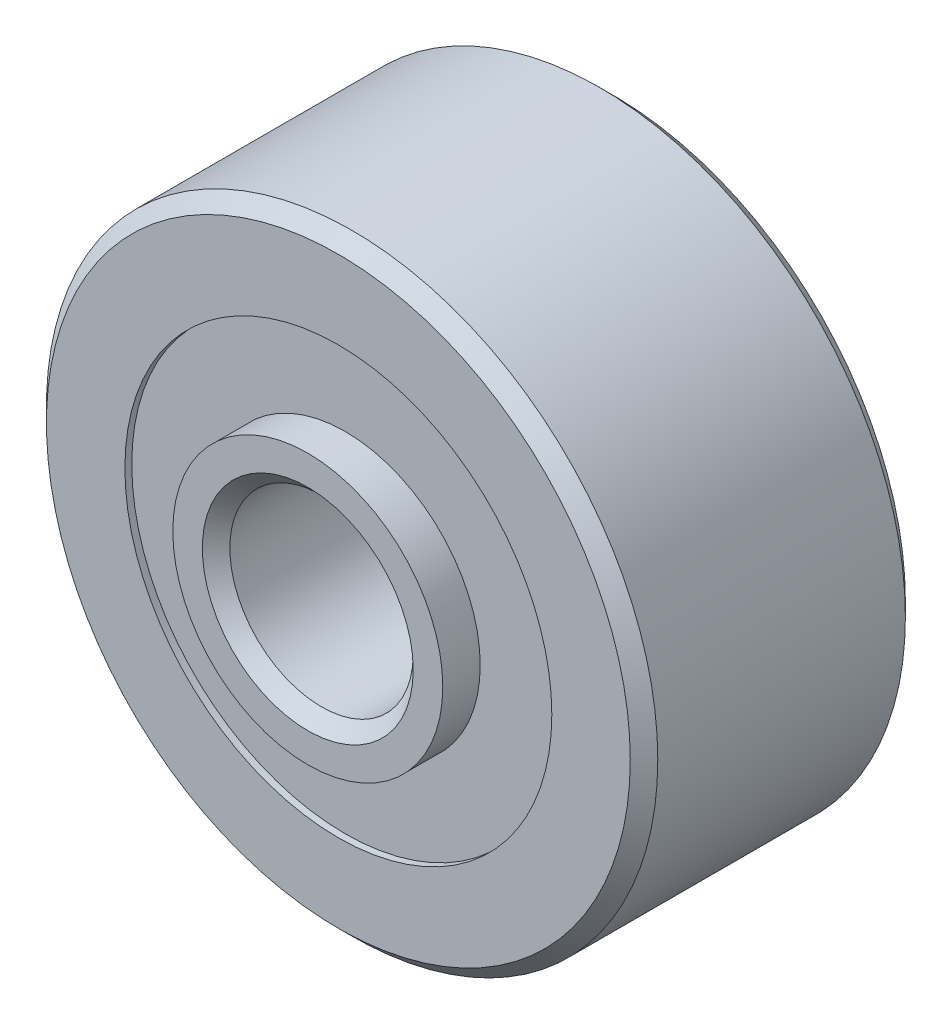
SolidWorks part; units mm, degrees
material "Cast Alloy Steel"
ref_plane "Front Plane" through (0, 0, 0) normal (0, 0, 1) x (1, 0, 0)
ref_plane "Top Plane" through (0, 0, 0) normal (0, 1, 0) x (1, 0, 0)
ref_plane "Right Plane" through (0, 0, 0) normal (1, 0, 0) x (0, 0, -1)
sketch "Sketch1" plane through (0, 0, 0) normal (1, 0, 0) x (0, 0, -1)
  line L0 (-1.7859, 0) -> (1.7859, 0) construction
  line L1 (0, 3.9688) -> (0, -3.9688) construction
  line L2 (1.6073, 3.9688) -> (-1.6073, 3.9688)
  line L3 (-1.6073, 3.9688) -> (-1.7859, 3.7902)
  line L4 (-1.7859, 3.7902) -> (-1.7859, 2.7716)
  line L5 (-1.7859, 2.7716) -> (-0.7938, 2.7716)
  line L6 (1.7859, 2.7716) -> (0.7937, 2.7716)
  line L7 (1.7859, 3.7902) -> (1.7859, 2.7716)
  line L8 (1.6073, 3.9688) -> (1.7859, 3.7902)
  line L9 (0, 3.9688) -> (0, 2.5797) construction
  line L10 (0, 2.5797) -> (0, 1.1906) construction
  arc A0 (-0.7938, 2.7716) -> (0.7937, 2.7716) centre (0, 2.5797) cw
  point P14 (0, 1.1906)
  dimension "Width" = 3.5719
  dimension "OD" = 7.9375
  dimension "D1" = 45
  dimension "D2" = 0.1786
  dimension "Shaft Dia" = 2.3813
  dimension "D3" = 1.5875
  dimension "D4" = 0.1919
revolve "Revolve1" add sketch "Sketch1" angle 360 about L0
sketch "Sketch3" plane through (0, 0, 0) normal (1, 0, 0) x (0, 0, -1)
  line L0 (-0.7937, 2.3878) -> (-2.1828, 2.3878) construction
  line L1 (-1.7859, 3.7902) -> (-1.7859, 2.7716) construction
  line L2 (-1.6073, 3.9688) -> (-1.7859, 3.7902) construction
  line L3 (-2.1828, 2.3878) -> (-2.1828, 1.3692) construction
  line L4 (-2.1828, 1.3692) -> (-2.1828, 1.7526)
  line L5 (-2.1828, 1.3692) -> (-2.0042, 1.1906)
  line L6 (-2.0042, 1.1906) -> (2.0042, 1.1906)
  line L7 (-2.1828, 1.7526) -> (2.1828, 1.7526)
  line L8 (2.0042, 1.1906) -> (2.1828, 1.3692)
  line L9 (-1.5875, 0) -> (1.3916, 0) construction
  line L10 (2.1828, 1.3692) -> (2.1828, 2.3878) construction
  line L11 (2.1828, 2.3878) -> (0.7937, 2.3878) construction
  line L12 (0, 3.9688) -> (0, -3.9688) construction
  line L13 (1.6073, 3.9688) -> (1.7859, 3.7902) construction
  line L18 (2.1828, 1.7526) -> (2.1828, 1.3692)
  arc A1 (0.7937, 2.3878) -> (-0.7937, 2.3878) centre (0, 2.5797) cw construction
  arc A2 (0.7937, 2.7716) -> (-0.7938, 2.7716) centre (0, 2.5797) ccw construction
  dimension "D1" = 45
  dimension "Ring" = 4.3656
  dimension "D2" = 3.5052
revolve "Revolve3" add sketch "Sketch3" angle 360 about L0
sketch "Sketch4" plane through (0, 0, 0) normal (1, 0, 0) x (0, 0, -1)
  line L0 (-0.8166, 2.5797) -> (0.8166, 2.5797)
  arc A2 (-0.8166, 2.5797) -> (0.8166, 2.5797) centre (0, 2.5797) cw
  arc A3 (0.7937, 2.7716) -> (-0.7938, 2.7716) centre (0, 2.5797) ccw construction
revolve "Revolve4" add sketch "Sketch4" angle 360 about L0
ref_axis "Axis1" through (0, 0, -1.7859) along (0, 0, 1)
pattern_circular "CirPattern1" count 8 every 45 about axis through (0, 0, -1.7859) along (0, 0, 1) of bodies 104
sketch "Sketch5" plane through (0, 0, 0) normal (1, 0, 0) x (0, 0, -1)
  line L0 (-1.7859, 2.7716) -> (-0.7938, 2.7716) construction
  line L1 (-1.6966, 2.7716) -> (-0.8166, 2.7716)
  line L2 (-1.6966, 2.7716) -> (-1.6966, 1.7526)
  line L3 (-1.6966, 1.7526) -> (-0.8166, 1.7526)
  line L4 (-0.8166, 2.7716) -> (-0.8166, 1.7526)
  line L5 (-2.1828, 1.7526) -> (2.1828, 1.7526) construction
  line L6 (1.7859, 2.7716) -> (0.7937, 2.7716) construction
  line L7 (1.6966, 2.7716) -> (0.8166, 2.7716)
  line L8 (1.6966, 2.7716) -> (1.6966, 1.7526)
  line L9 (1.6966, 1.7526) -> (0.8166, 1.7526)
  line L10 (0.8166, 2.7716) -> (0.8166, 1.7526)
  line L12 (-1.6073, 3.9688) -> (-1.7859, 3.7902) construction
  point P18 (-1.6966, 3.8795)
revolve "Revolve5" add sketch "Sketch5" angle 360 about L0
equation "\"D2@Sketch1\" = \"Width@Sketch1\"*.05"
equation "\"D3@Sketch1\" = \"Width@Sketch1\"/2.25"
equation "\"D4@Sketch1\" = (((\"OD@Sketch1\"-\"Width@Sketch1\")/2)/3.25)/3.5"
equation "\"D2@CirPattern1\" = 360/\"Balls@CirPattern1\""
